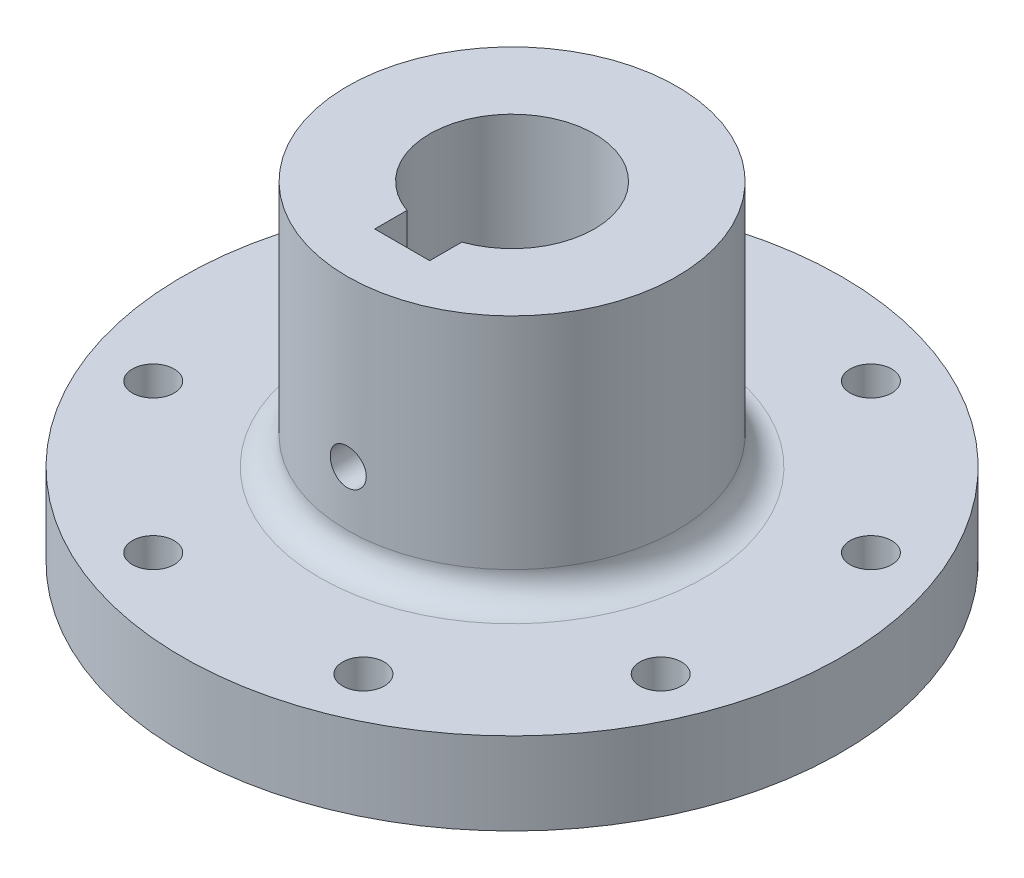
SolidWorks part; units mm, degrees
material "6061-T6 (SS)"
ref_plane "Front Plane" through (0, 0, 0) normal (0, 0, 1) x (1, 0, 0)
ref_plane "Top Plane" through (0, 0, 0) normal (0, 1, 0) x (1, 0, 0)
ref_plane "Right Plane" through (0, 0, 0) normal (1, 0, 0) x (0, 0, -1)
sketch "Sketch1" plane through (0, 0, 0) normal (0, 1, 0) x (1, 0, 0)
  circle A0 centre (0, 0) radius 38.1
  circle A1 centre (0, 0) radius 9.525
  dimension "D1" = 76.2
  dimension "D2" = 19.05
extrude "Boss-Extrude1" add sketch "Sketch1" along normal blind 38.1
hole_wizard "#10-32 Tapped Hole1" positions "Sketch3" profile "Sketch2" tap size "#10-32" standard "Ansi Inch" end condition through all
sketch "Sketch3" plane through (0, 38.1, 0) normal (0, 1, 0) x (-1, 0, 0)
  line L0 (38.1, 0) -> (0, 0) construction
  line L1 (0, 0) -> (29.3332, -12.1502) construction
  circle A0 centre (0, 0) radius 38.1 construction
  point P0 (29.3332, -12.1502)
  dimension "D1" = 31.75
  dimension "D2" = 22.5
sketch "Sketch2" plane through (-29.3332, 38.1, -12.1502) normal (1, 0, 0) x (0, 0, 1)
  line L0 (0, 0) -> (0, 38.1)
  line L1 (0, 38.1) -> (2.413, 38.1)
  line L2 (2.413, 38.1) -> (2.413, 0)
  line L5 (2.413, 0) -> (0, 0)
  line L11 (0, -6.35) -> (0, 107.95) construction
  dimension "Thread Major Dia." = 4.826
  dimension "Thru Tap Drill Depth" = 38.1
pattern_circular "CirPattern1" count 8 over 360 about axis through (0, 38.1, 0) along (0, -1, 0) of "#10-32 Tapped Hole1"
sketch "Sketch4" plane through (0, 38.1, 0) normal (0, 1, 0) x (1, 0, 0)
  line L1 (-3.175, -12.7) -> (3.175, -12.7)
  line L2 (-3.175, -12.7) -> (-3.175, -6.35)
  line L3 (-3.175, -6.35) -> (3.175, -6.35)
  line L4 (3.175, -12.7) -> (3.175, -6.35)
  line L5 (-3.175, -12.7) -> (3.175, -6.35) construction
  line L6 (-3.175, -6.35) -> (3.175, -12.7) construction
  circle A0 centre (0, 0) radius 9.525 construction
  point P0 (0, -9.525)
  dimension "D1" = 6.35
  dimension "D2" = 6.35
extrude "Cut-Extrude1" cut sketch "Sketch4" against normal through all
hole_wizard "#8-32 Tapped Hole1" positions "Sketch6" profile "Sketch5" tap size "#8-32" standard "ANSI Inch" end condition through all
sketch "Sketch6" plane through (0, 0, 12.7) normal (0, 0, -1) x (-1, 0, 0)
  line L0 (3.175, 0) -> (-3.175, 0) construction
  line L1 (3.175, 0) -> (3.175, 38.1) construction
  point P0 (0, 19.05)
  dimension "D1" = 19.05
  dimension "D2" = 3.175
sketch "Sketch5" plane through (0, 19.05, 12.7) normal (1, 0, 0) x (0, 1, 0)
  line L0 (0, 0) -> (0, 25.4)
  line L1 (0, 25.4) -> (2.0828, 25.4)
  line L2 (2.0828, 25.4) -> (2.0828, 0)
  line L5 (2.0828, 0) -> (0, 0)
  line L11 (0, -6.35) -> (0, 107.95) construction
  dimension "Thread Major Dia." = 4.1656
  dimension "Thru Tap Drill Depth" = 25.4
sketch "Sketch7" plane through (0, 38.1, 0) normal (0, 1, 0) x (1, 0, 0)
  circle A0 centre (0, 0) radius 19.05
  dimension "D1" = 38.1
extrude "Cut-Extrude2" cut sketch "Sketch7" against normal offset from surface (28.575 mm away) 9.525 flip side to cut up to face at (-29.3332, 0, 14.5632)
fillet "Fillet1" radius 3.175 1 edges at (0, 9.525, 19.05)
